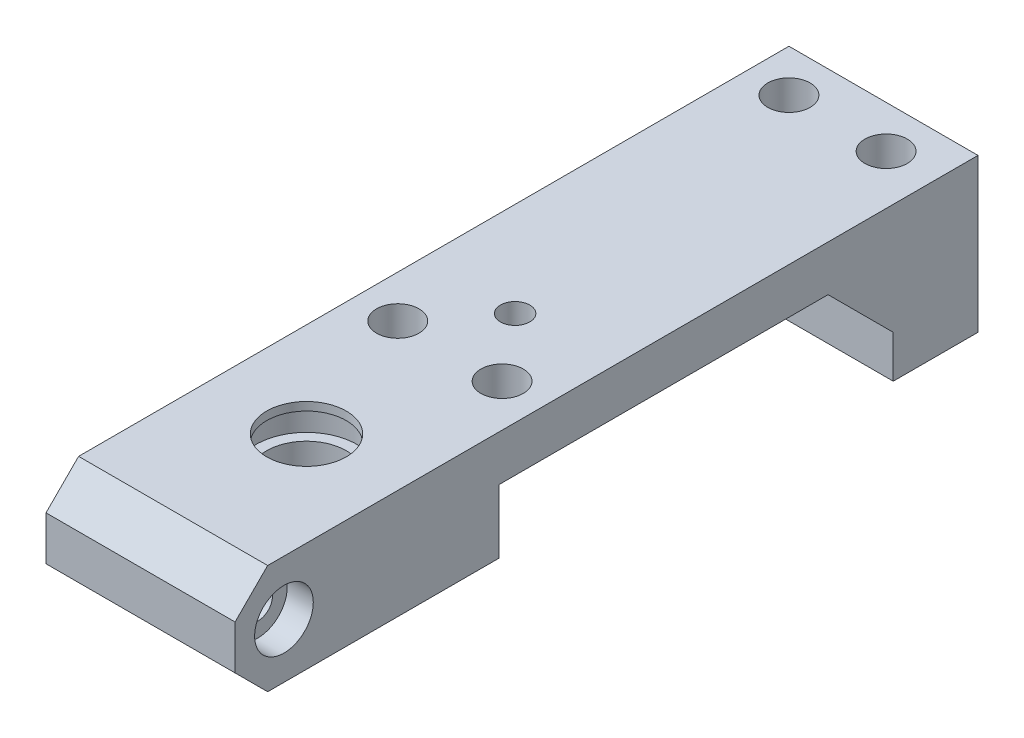
SolidWorks part; units mm, degrees
ref_plane "Front Plane" through (0, 0, 0) normal (0, 0, 1) x (1, 0, 0)
ref_plane "Top Plane" through (0, 0, 0) normal (0, 1, 0) x (1, 0, 0)
ref_plane "Right Plane" through (0, 0, 0) normal (1, 0, 0) x (0, 0, -1)
sketch "Sketch1" plane through (0, 0, 0) normal (0, 1, 0) x (1, 0, 0)
  line L0 (0, 60) -> (0, 0) construction
  line L1 (0, 0) -> (16, 0) construction
  line L3 (-6.5, 66.5) -> (22.5, 66.5)
  line L4 (-6.5, 66.5) -> (-6.5, -7)
  line L5 (-6.5, -7) -> (22.5, -7)
  line L6 (22.5, 66.5) -> (22.5, -7)
  circle A0 centre (0, 0) radius 3.25
  circle A1 centre (16, 0) radius 3.25
  circle A2 centre (0, 60) radius 3.25
  circle A3 centre (14.9024, 60) radius 3.25
  circle A4 centre (8, 10) radius 2.25
  point P15 (8, 0)
  dimension "D1" = 6.5
  dimension "D9" = 4.5
  dimension "D2" = 16
  dimension "D3" = 60
  dimension "D4" = 60
  dimension "D5" = 7
  dimension "D6" = 6.5
  dimension "D7" = 6.5
  dimension "D8" = 6.5
  dimension "D10" = 10
extrude "Boss-Extrude1" add sketch "Sketch1" along normal blind 7
sketch "Sketch2" plane through (0, 0, 0) normal (0, -1, 0) x (-1, 0, 0)
  circle A0 centre (-8, 10) radius 4.5
  dimension "D1" = 9
extrude "Cut-Extrude1" cut sketch "Sketch2" against normal blind 3
sketch "Sketch3" plane through (0, 0, 0) normal (0, -1, 0) x (-1, 0, 0)
  line L0 (6.5, 66.5) -> (6.5, -7) construction
  line L1 (-22.5, 66.5) -> (6.5, 66.5)
  line L2 (-22.5, 66.5) -> (-22.5, 53.5)
  line L3 (-22.5, 53.5) -> (6.5, 53.5)
  line L4 (6.5, 66.5) -> (6.5, 53.5)
  circle A0 centre (-14.9024, 60) radius 3.25 construction
  circle A1 centre (-14.9024, 60) radius 3.25
  circle A2 centre (0, 60) radius 3.25
  dimension "D1" = 6.5
extrude "Boss-Extrude2" add sketch "Sketch3" along normal blind 16.5
ref_plane "Plane1" through (8, 0, 0) normal (1, 0, 0) x (0, 0, -1)
sketch "Sketch4" plane through (8, 0, 0) normal (1, 0, 0) x (0, 0, -1)
  line L0 (-15.9, 7) -> (-11.5017, 7)
  line L1 (-15.9, 7) -> (-15.9, 5.7282)
  line L2 (-15.9, 5.7282) -> (-14.25, 5.7282)
  line L3 (-14.25, 5.7282) -> (-14.25, 1.7282)
  line L4 (-14.25, 1.7282) -> (-15.9, 1.7282)
  line L5 (-15.9, 1.7282) -> (-15.9, -3.7718)
  line L6 (-15.9, -3.7718) -> (-14.25, -3.7718)
  line L7 (-14.25, -3.7718) -> (-14.25, -9.7718)
  line L8 (-11.5017, 7) -> (-11.5017, -9.7718)
  line L9 (-22, 7) -> (-22, 3.1466) construction
  line L12 (-11.5017, -9.7718) -> (-14.25, -9.7718)
  dimension "D2" = 7.75
  dimension "D3" = 6
  dimension "D4" = 4
  dimension "D5" = 5.5
  dimension "D6" = 6.1
revolve "Revolve1" add sketch "Sketch4" angle 360 about L9
sketch "Sketch5" plane through (0, 7, 0) normal (0, 1, 0) x (1, 0, 0)
  line L0 (-6.5, -7) -> (-6.5, -22)
  line L1 (-6.5, -22) -> (-6.5, -37.4557)
  line L2 (-6.5, -37.4557) -> (22.5, -37.4557)
  line L3 (22.5, -37.4557) -> (22.5, -7)
  line L4 (-6.5, 66.5) -> (-6.5, -7) construction
  line L5 (-6.5, -7) -> (22.5, -7)
  circle A0 centre (8, -22) radius 10.4983
extrude "Boss-Extrude3" add sketch "Sketch5" against normal up to surface (16.7718 mm away) up to face at (8, -9.7718, 32.4983)
chamfer "Chamfer1" distance 10 angle 45 1 edges at (8, 0, -53.5)
sketch "Sketch6" plane through (0, 0, 37.4557) normal (0, 0, 1) x (1, 0, 0)
  line L1 (-6.5, 7) -> (22.5, 7)
  line L2 (-6.5, 7) -> (-6.5, -9.7718)
  line L3 (-6.5, -9.7718) -> (22.5, -9.7718)
  line L4 (22.5, 7) -> (22.5, -9.7718)
extrude "Boss-Extrude4" add sketch "Sketch6" along normal blind 10
sketch "Sketch7" plane through (22.5, 0, 0) normal (1, 0, 0) x (0, 0, -1)
  line L0 (-47.4557, 7) -> (-32.4557, -9.7718) construction
  line L1 (-7, -9.7718) -> (-47.4557, -9.7718) construction
  circle A0 centre (-39.9557, -1.3859) radius 2.25
  dimension "D2" = 4.5
  dimension "D1" = 15
extrude "Cut-Extrude2" cut sketch "Sketch7" against normal through all both and the other way through all
sketch "Sketch8" plane through (22.5, 0, 0) normal (1, 0, 0) x (0, 0, -1)
  circle A0 centre (-39.9557, -1.3859) radius 4.5
  dimension "D1" = 9
extrude "Cut-Extrude3" cut sketch "Sketch8" against normal blind 4
sketch "Sketch9" plane through (-6.5, 0, 0) normal (-1, 0, 0) x (0, 0, 1)
  line L1 (43.9971, -1.3859) -> (41.9764, 2.1141)
  line L2 (41.9764, 2.1141) -> (37.935, 2.1141)
  line L3 (37.935, 2.1141) -> (35.9142, -1.3859)
  line L4 (35.9142, -1.3859) -> (37.935, -4.8859)
  line L5 (37.935, -4.8859) -> (41.9764, -4.8859)
  line L6 (41.9764, -4.8859) -> (43.9971, -1.3859)
  circle A0 centre (39.9557, -1.3859) radius 3.5 construction
  dimension "D1" = 7
extrude "Cut-Extrude4" cut sketch "Sketch9" against normal blind 3
chamfer "Chamfer2" distance 5 angle 45 2 edges at (8, -9.7718, 47.4557) (8, 7, 47.4557)
